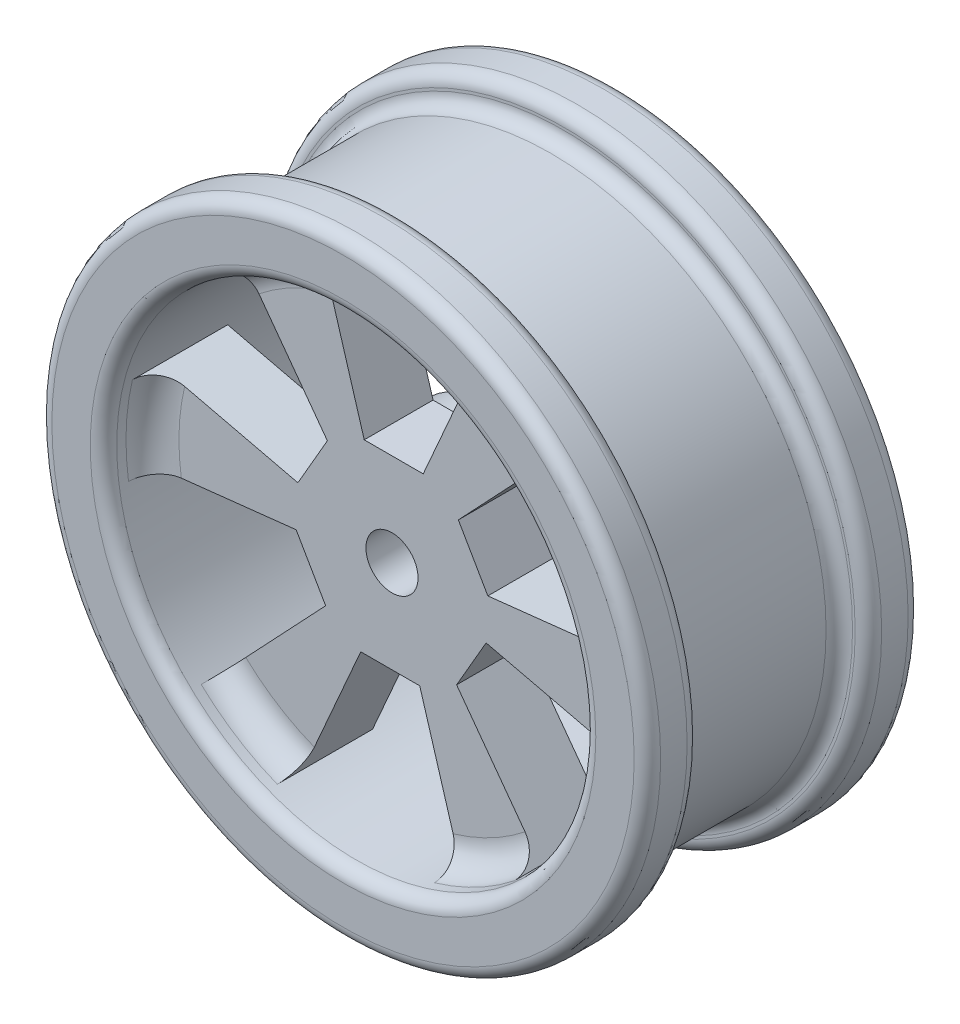
SolidWorks part; units mm, degrees
material "ABS"
ref_plane "Front Plane" through (0, 0, 0) normal (0, 0, 1) x (1, 0, 0)
ref_plane "Top Plane" through (0, 0, 0) normal (0, 1, 0) x (1, 0, 0)
ref_plane "Right Plane" through (0, 0, 0) normal (1, 0, 0) x (0, 0, -1)
sketch "Sketch1" plane through (0, 0, 0) normal (1, 0, 0) x (0, 0, -1)
  line L0 (0, 0) -> (59.5506, 0) construction
  line L1 (0, 0) -> (0, 22.987) construction
  line L2 (0, 22.987) -> (15.24, 22.987) construction
  line L3 (17.78, 25.527) -> (17.78, 27.94)
  line L4 (16.51, 29.21) -> (13.97, 29.21)
  line L5 (12.7, 27.94) -> (12.7, 27.686)
  line L6 (11.43, 26.416) -> (-2.159, 26.416)
  line L7 (-3.429, 27.686) -> (-3.429, 27.94)
  line L8 (-4.699, 29.21) -> (-7.239, 29.21)
  line L9 (-8.509, 27.94) -> (-8.509, 24.257)
  line L10 (-7.239, 22.987) -> (-6.35, 22.987)
  line L11 (-3.81, 20.447) -> (-3.81, 0)
  line L12 (-3.81, 0) -> (0, 0)
  line L13 (2.794, 22.987) -> (15.24, 22.987)
  line L14 (2.794, 22.987) -> (2.794, 8.4709)
  line L15 (2.794, 8.4709) -> (5.715, 8.4709)
  line L16 (5.715, 8.4709) -> (5.715, 0)
  line L17 (5.715, 0) -> (0, 0)
  arc A0 (-6.35, 22.987) -> (-3.81, 20.447) centre (-6.35, 20.447) cw
  arc A1 (16.51, 29.21) -> (17.78, 27.94) centre (16.51, 27.94) cw
  arc A2 (13.97, 29.21) -> (12.7, 27.94) centre (13.97, 27.94) ccw
  arc A3 (-7.239, 29.21) -> (-8.509, 27.94) centre (-7.239, 27.94) ccw
  arc A4 (-4.699, 29.21) -> (-3.429, 27.94) centre (-4.699, 27.94) cw
  arc A5 (12.7, 27.686) -> (11.43, 26.416) centre (11.43, 27.686) cw
  arc A6 (-3.429, 27.686) -> (-2.159, 26.416) centre (-2.159, 27.686) ccw
  arc A7 (-7.239, 22.987) -> (-8.509, 24.257) centre (-7.239, 24.257) cw
  arc A8 (17.78, 25.527) -> (15.24, 22.987) centre (15.24, 25.527) cw
  point P22 (12.7, 29.21)
  point P29 (12.7, 26.416)
  point P36 (17.78, 22.987)
  dimension "D8" = 2.54
  dimension "D9" = 1.27
  dimension "D10" = 2.54
  dimension "D11" = 45.974
  dimension "D1" = 58.42
  dimension "D2" = 2.794
  dimension "D3" = 14.986
  dimension "D4" = 5.08
  dimension "D5" = 3.81
  dimension "D6" = 26.289
  dimension "D7" = 17.78
  dimension "D12" = 16.9418
  dimension "D13" = 12.065
revolve "Body" add sketch "Sketch1" angle 360 about L0
sketch "Sketch2" plane through (0, 0, 0) normal (0, 0, 1) x (1, 0, 0)
  line L0 (-2.6636, 8.89) -> (2.9969, 8.89)
  line L1 (3.3042, -6.0895) -> (6.9258, -0.1832)
  line L2 (6.9258, -0.1832) -> (3.6216, 5.9063)
  line L3 (3.6216, 5.9063) -> (-3.3042, 6.0895)
  line L4 (-3.3042, 6.0895) -> (-6.9258, 0.1832)
  line L5 (-6.9258, 0.1832) -> (-3.6216, -5.9063)
  line L6 (-3.6216, -5.9063) -> (3.3042, -6.0895)
  line L7 (2.9969, 8.89) -> (8.47, 21.3696)
  line L8 (-2.6636, 8.89) -> (-6.5976, 22.0199)
  circle A0 centre (0, 0) radius 6 construction
  circle A1 centre (0, 0) radius 22.987 construction
  arc A2 (-6.5976, 22.0199) -> (8.47, 21.3696) centre (0, 0) cw
  circle A3 centre (0, 0) radius 2.5
  circle A4 centre (0, 0) radius 6.9282 construction
  dimension "D1" = 5
  dimension "D2" = 12
  dimension "D3" = 8.89
extrude "Nut" cut sketch "Sketch2" along normal blind 4.572 from surface contours L2 L3 L4 L5 L6 L1 starting at face at (8.4709, 0, -5.715)
extrude "Spokes" cut sketch "Sketch2<3>" against normal through all both and the other way through all contours L7 A2 L8 L0
sketch "Sketch2<3>" plane through (0, 0, 0) normal (0, 0, 1) x (1, 0, 0) same geometry as "Sketch2"
pattern_circular "CirPattern1" count 6 over 360 about axis through (0, 0, 0) along (0, 0, 1) of "Spokes"
extrude "Axle" cut sketch "Sketch2<4>" along normal through all both and the other way through all contours A3
sketch "Sketch2<4>" plane through (0, 0, 0) normal (0, 0, 1) x (1, 0, 0) same geometry as "Sketch2"
